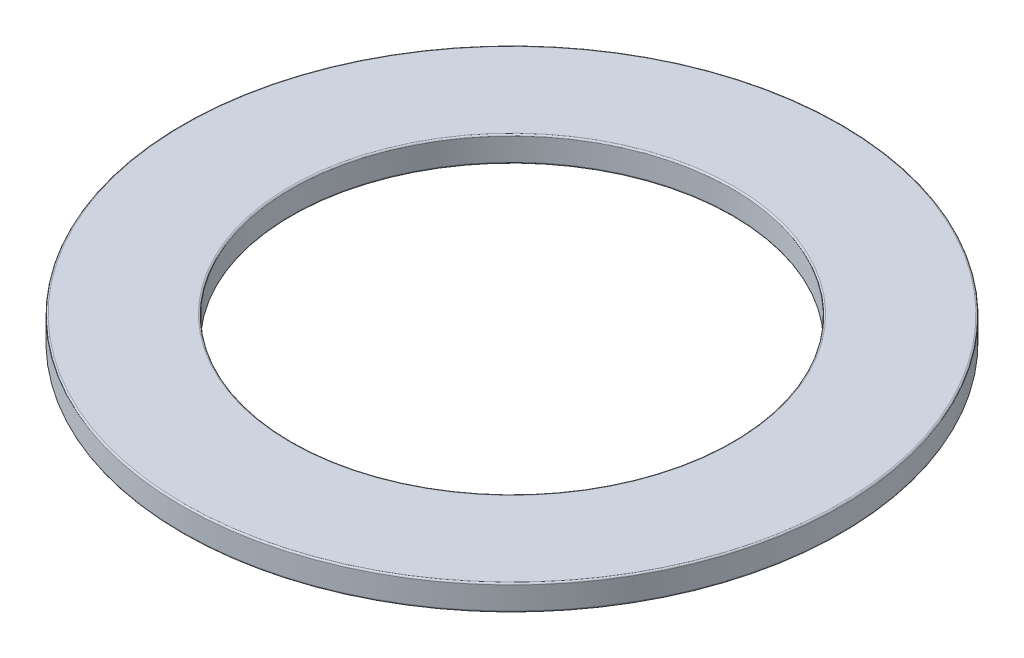
SolidWorks part; units mm, degrees
ref_plane "Front Plane" through (0, 0, 0) normal (0, 0, 1) x (1, 0, 0)
ref_plane "Top Plane" through (0, 0, 0) normal (0, 1, 0) x (1, 0, 0)
ref_plane "Right Plane" through (0, 0, 0) normal (1, 0, 0) x (0, 0, -1)
sketch "Sketch1" plane through (0, 0, 0) normal (1, 0, 0) x (0, 0, -1)
  line L0 (-23.8125, 0) -> (23.8125, 0) construction
  line L1 (0, -5.5499) -> (0, 5.5499) construction
  line L2 (-23.8125, 1.1562) -> (-15.9131, 1.1562)
  line L3 (-23.8125, 1.1562) -> (-23.8125, -1.1562)
  line L4 (-23.8125, -1.1562) -> (-15.9131, -1.1562)
  line L5 (-15.9131, 1.1562) -> (-15.9131, -1.1562)
  line L6 (-19.8628, 1.85) -> (-19.8628, -1.85) construction
  circle A0 centre (-19.8628, 0) radius 1.85 construction
  point P13 (-19.8628, 1.1562)
  dimension "D1" = 3.6999
  dimension "OD" = 47.625
  dimension "Shaft Dia" = 31.8262
  dimension "Th" = 11.0998
  dimension "D2" = 2.3125
sketch "Sketch3" plane through (0, 0, 0) normal (1, 0, 0) x (0, 0, -1)
  line L0 (-19.8628, 1.85) -> (-19.8628, -1.85)
  arc A0 (-19.8628, 1.85) -> (-19.8628, -1.85) centre (-19.8628, 0) ccw
  circle A1 centre (-19.8628, 0) radius 1.85 construction
sketch "Sketch2" plane through (0, 0, 0) normal (1, 0, 0) x (0, 0, -1)
  line L0 (-19.8628, 1.85) -> (-19.8628, -1.85)
  arc A0 (-19.8628, 1.85) -> (-19.8628, -1.85) centre (-19.8628, 0) ccw
  circle A2 centre (-19.8628, 0) radius 1.85 construction
ref_axis "Axis1" through (0, 5.5499, 0) along (0, -1, 0)
sketch "Sketch4" plane through (0, 0, 0) normal (1, 0, 0) x (0, 0, -1)
  line L0 (-23.8125, 1.1562) -> (-23.8125, -1.1562) construction
  line L5 (-23.8125, -5.5499) -> (-15.9131, -5.5499)
  line L6 (-23.8125, -5.5499) -> (-23.8125, -3.6999)
  line L7 (-23.8125, -3.6999) -> (-15.9131, -3.6999)
  line L8 (-15.9131, -5.5499) -> (-15.9131, -3.6999)
  line L11 (0, 0) -> (-23.8125, 0) construction
  line L12 (-23.8125, 0) -> (23.8125, 0) construction
  dimension "D1" = 1.85
revolve "Revolve3" add sketch "Sketch4" angle 360 about L1
fillet "Fillet3" radius 0.111 4 edges at (0, -5.5499, -15.9131) (0, -3.6999, -15.9131) (0, -5.5499, -23.8125) (0, -3.6999, -23.8125)
